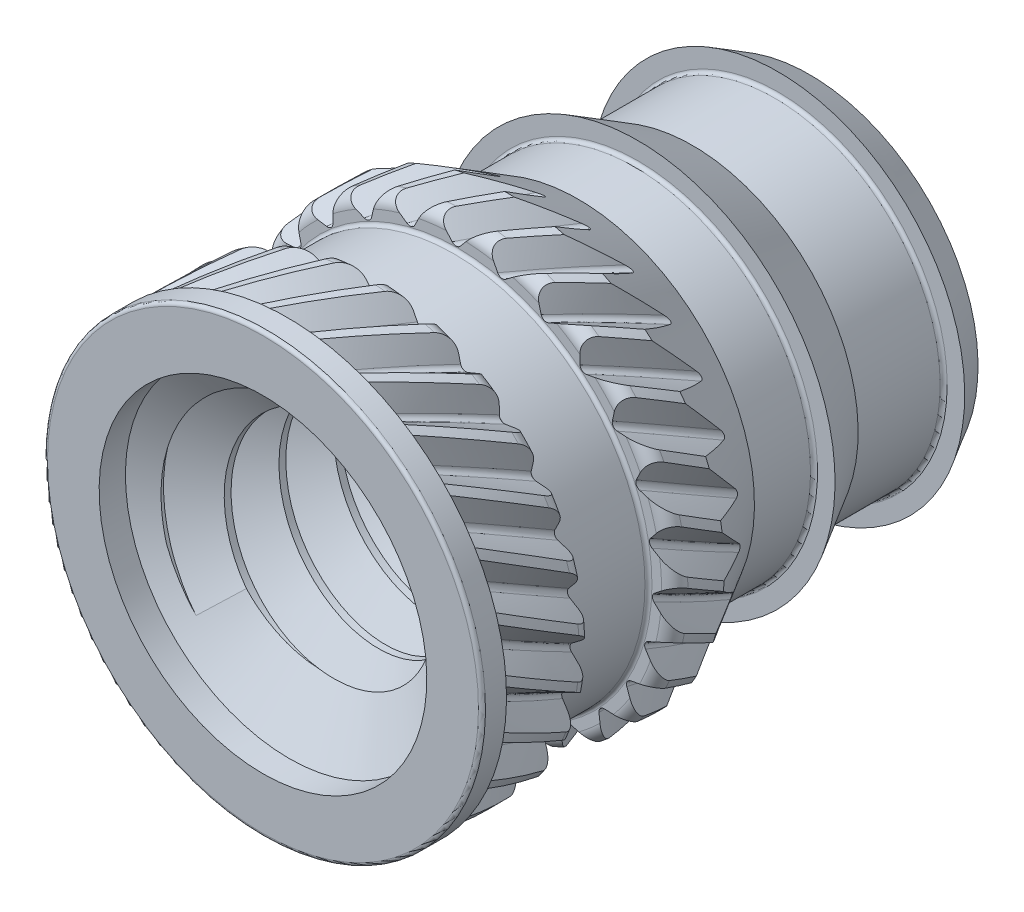
SolidWorks part; units mm, degrees
ref_plane "Front Plane" through (0, 0, 0) normal (0, 0, 1) x (1, 0, 0)
ref_plane "Top Plane" through (0, 0, 0) normal (0, 1, 0) x (1, 0, 0)
ref_plane "Right Plane" through (0, 0, 0) normal (1, 0, 0) x (0, 0, -1)
sketch "Sketch1" plane through (0, 0, 0) normal (1, 0, 0) x (0, 0, -1)
  line L0 (3.9624, 0) -> (-3.9624, 0) construction
  line L1 (-3.9624, 3.175) -> (-3.9624, -3.175) construction
  line L3 (3.9624, 2.4411) -> (3.9624, -2.4411) construction
  line L4 (-3.9624, 3.175) -> (-3.6068, 3.175) construction
  line L5 (-3.6068, 3.175) -> (-3.6068, 3.1496) construction
  line L6 (-3.6068, 3.1496) -> (-2.3368, 3.1496) construction
  line L7 (-2.3368, 3.1496) -> (-2.3368, 2.7686) construction
  line L8 (-2.3368, 2.7686) -> (-1.143, 2.7686) construction
  line L9 (-1.143, 2.7686) -> (-1.143, 3.1496) construction
  line L10 (-1.143, 3.1496) -> (-0.4243, 3.1496) construction
  line L12 (-3.5814, -2.3749) -> (-3.4128, -2.0828) construction
  line L13 (-3.4128, -2.0828) -> (3.8481, -2.0828) construction
  line L14 (3.8481, -2.0828) -> (3.9624, -2.1971) construction
  line L15 (-3.4128, -2.0828) -> (-3.4128, -1.2891) construction
  line L16 (-3.5814, -2.3749) -> (-3.9624, -2.3749) construction
  line L17 (-0.4243, 3.1496) -> (0.6096, 2.5527) construction
  line L18 (0.6096, 2.5527) -> (1.4732, 2.5527) construction
  line L19 (1.4732, 2.5527) -> (1.4732, 2.8575) construction
  line L20 (1.4732, 2.8575) -> (2.2651, 2.4003) construction
  line L21 (2.2651, 2.4003) -> (3.5052, 2.4003) construction
  line L22 (3.5052, 2.4003) -> (3.5052, 2.7051) construction
  line L23 (3.5052, 2.7051) -> (3.9624, 2.4411) construction
  point P4 (0, 0)
  dimension "Diameter (A)" = 6.35
  dimension "Installed Length" = 7.9248
  dimension "Head Length" = 0.3556
  dimension "Knurl Band OD" = 6.2992
  dimension "Knurl Band_1 Length" = 1.27
  dimension "Relief Depth" = 0.381
  dimension "Relief Length" = 1.1938
  dimension "Thread Size" = 4.1656
  dimension "Thread Pitch" = 0.7937
  dimension "C'Sink Dia (B)" = 4.3942
  dimension "C'Sink (A)" = 60
  dimension "C'Bore" = 4.7498
  dimension "C'Bore Depth" = 0.381
  dimension "Barb Angle" = 30
  dimension "End Barb Length" = 0.4572
  dimension "End Barb OD" = 5.4102
  dimension "End Barb Relief" = 4.8006
  dimension "Barb_2 OD" = 5.715
  dimension "Barbed Length" = 2.4892
  dimension "Barb_2 Relief" = 5.1054
  dimension "Barb_2 Relief Length" = 0.8636
  dimension "C'Sink (B)" = 45
sketch "Sketch2" plane through (0, 0, 0) normal (1, 0, 0) x (0, 0, -1)
  line L0 (-2.5273, 3.1496) -> (-2.5273, 2.7686) construction
  line L3 (3.5052, 2.7051) -> (3.9624, 2.4411) construction
  line L15 (3.5052, 2.4003) -> (3.5052, 2.7051) construction
  line L27 (2.2651, 2.4003) -> (3.5052, 2.4003) construction
  line L31 (1.4732, 2.8575) -> (2.2651, 2.4003) construction
  line L33 (1.4732, 2.5527) -> (1.4732, 2.8575) construction
  line L35 (0.6096, 2.5527) -> (1.4732, 2.5527) construction
  line L36 (-0.4243, 3.1496) -> (0.6096, 2.5527) construction
  line L37 (-1.143, 3.1496) -> (-0.4243, 3.1496) construction
  line L38 (-1.143, 2.7686) -> (-1.143, 3.1496) construction
  line L39 (-2.3368, 2.7686) -> (-1.143, 2.7686) construction
  line L40 (-2.3368, 3.1496) -> (-2.3368, 2.7686) construction
  line L41 (-3.6068, 3.1496) -> (-2.3368, 3.1496) construction
  line L42 (-3.6068, 3.175) -> (-3.6068, 3.1496) construction
  line L43 (-3.9624, 3.175) -> (-3.6068, 3.175) construction
  line L44 (3.5052, 2.7051) -> (3.9624, 2.4411)
  line L45 (3.5052, 2.4511) -> (3.5052, 2.7051)
  line L46 (2.2651, 2.4003) -> (3.4544, 2.4003)
  line L47 (1.4732, 2.8575) -> (2.2651, 2.4003)
  line L48 (1.4732, 2.6035) -> (1.4732, 2.8575)
  line L49 (0.6096, 2.5527) -> (1.4224, 2.5527)
  line L50 (-0.4243, 3.1496) -> (0.6096, 2.5527)
  line L51 (-0.9525, 3.1496) -> (-0.4243, 3.1496)
  line L52 (-1.143, 2.8194) -> (-1.143, 2.9591)
  line L53 (-2.286, 2.7686) -> (-1.1938, 2.7686)
  line L54 (-2.3368, 2.9591) -> (-2.3368, 2.8194)
  line L55 (-3.6068, 3.1496) -> (-2.5273, 3.1496)
  line L56 (-3.6068, 3.175) -> (-3.6068, 3.1496)
  line L57 (-3.9116, 3.175) -> (-3.6068, 3.175)
  line L58 (-3.9624, 0) -> (3.9624, 0) construction
  line L59 (-3.9624, 3.1242) -> (-3.9624, 2.3749)
  line L60 (-3.9624, 3.175) -> (-3.9624, -3.175) construction
  line L61 (-3.9624, 2.3749) -> (-3.5814, 2.3749)
  line L62 (-3.5814, 2.3749) -> (-3.4128, 2.0828)
  line L63 (-3.4128, 2.0828) -> (3.8481, 2.0828)
  line L64 (3.8481, 2.0828) -> (3.9624, 2.1971)
  line L65 (3.9624, 2.4411) -> (3.9624, -2.4411) construction
  line L66 (3.9624, 2.1971) -> (3.9624, 2.4411)
  line L67 (-3.5814, -2.3749) -> (-3.9624, -2.3749) construction
  line L68 (-3.5814, -2.3749) -> (-3.4128, -2.0828) construction
  line L69 (3.8481, -2.0828) -> (3.9624, -2.1971) construction
  line L70 (0, -2.0828) -> (0, 2.0828) construction
  line L71 (-3.4128, -2.0828) -> (3.8481, -2.0828) construction
  arc A1 (3.5052, 2.4511) -> (3.4544, 2.4003) centre (3.4544, 2.4511) cw
  arc A2 (1.4732, 2.6035) -> (1.4224, 2.5527) centre (1.4224, 2.6035) cw
  arc A3 (-0.9525, 3.1496) -> (-1.143, 2.9591) centre (-0.9525, 2.9591) ccw
  arc A4 (-2.3368, 2.9591) -> (-2.5273, 3.1496) centre (-2.5273, 2.9591) ccw
  arc A5 (-3.9116, 3.175) -> (-3.9624, 3.1242) centre (-3.9116, 3.1242) ccw
  arc A6 (-1.143, 2.8194) -> (-1.1938, 2.7686) centre (-1.1938, 2.8194) cw
  arc A7 (-2.286, 2.7686) -> (-2.3368, 2.8194) centre (-2.286, 2.8194) cw
  point P64 (0, 0)
  dimension "D1" = 0.0508
  dimension "D2" = 0.0508
  dimension "D3" = 0.0508
  dimension "Knurl Length" = 4.2164
revolve "Revolve1" add sketch "Sketch2" angle 360 about L58
sketch "Sketch3" plane through (0, 0, 0) normal (0, 0, 1) x (1, 0, 0)
  line L0 (0, -2.0828) -> (0, 0) construction
  line L1 (0, 0) -> (1.0414, -1.8038) construction
  line L2 (0, 2.4411) -> (0, -2.4411) construction
  circle A0 centre (0, 0) radius 2.0828 construction
  point P0 (1.0414, -1.8038)
  dimension "D1" = 30
sketch "Sketch4" plane through (0, 0, 3.9624) normal (0, 0, 1) x (1, 0, 0)
  circle A0 centre (0, 0) radius 2.0828 construction
  circle A1 centre (0, 0) radius 2.0828
curve "Helix/Spiral1" pitch 0.7937 height 8.7186 radius 2.0828 centre (0, 0, 3.9624) axis (0, 0, -1) start towards (0, 1, 0)
sketch "Sketch5" plane through (0, 0, 0) normal (1, 0, 0) x (0, 0, -1)
  line L0 (-4.7313, 2.1258) -> (-4.3345, 1.4384) construction
  line L1 (-4.3345, 1.4384) -> (-3.9376, 2.1258) construction
  line L2 (-3.9376, 2.1258) -> (-4.7313, 2.1258) construction
  line L3 (-4.6817, 2.0398) -> (-3.9872, 2.0398) construction
  line L4 (-4.3345, 2.1258) -> (-4.3345, 2.0398) construction
  line L5 (-4.3345, 2.0398) -> (-4.3345, 1.5243) construction
  line L6 (-4.3345, 1.5243) -> (-4.3345, 1.4384) construction
  line L7 (-4.3841, 1.5243) -> (-4.2849, 1.5243)
  line L8 (-4.7065, 2.0828) -> (-3.9624, 2.0828)
  line L9 (-4.2849, 1.5243) -> (-3.9624, 2.0828)
  line L10 (-4.3841, 1.5243) -> (-4.7065, 2.0828)
  line L15 (3.8481, 2.0828) -> (-3.4128, 2.0828) construction
  line L16 (-3.9624, 3.175) -> (-3.9624, -3.175) construction
  point P12 (-4.3345, 2.0828)
  dimension "D1" = 0.7937
  dimension "D2" = 0.0992
sweep "Sweep1" add profiles "Sketch5" path "Helix/Spiral1"
ref_plane "Plane1" through (0, 0, 3.5814) normal (0, 0, 1) x (1, 0, 0)
sketch "Sketch6" plane through (0, 0, 3.5814) normal (0, 0, 1) x (1, 0, 0)
  circle A0 centre (0, 0) radius 2.3749
extrude "Cut-Extrude1" cut sketch "Sketch6" against normal through all draft 60 and the other way through all
sketch "Sketch7" plane through (0, 0, -3.9624) normal (0, 0, -1) x (-1, 0, 0)
  circle A1 centre (0, 0) radius 2.1971
  circle A2 centre (0, 0) radius 2.1971 construction
extrude "Cut-Extrude2" cut sketch "Sketch7" against normal through all draft 45 and the other way through all
ref_plane "Plane2" through (0, 0, 3.6068) normal (0, 0, 1) x (1, 0, 0)
sketch "Sketch8" plane through (0, 0, 3.6068) normal (0, 0, 1) x (1, 0, 0)
  circle A1 centre (0, 0) radius 3.1496
  circle A2 centre (0, 0) radius 3.1496 construction
curve "Helix/Spiral2" pitch 33.7312 height 4.2164 radius 3.1496 centre (0, 0, 3.6068) axis (0, 0, -1) start towards (0, 1, 0)
sketch "Sketch9" plane through (0, 0, 3.6068) normal (0, 0, 1) x (1, 0, 0)
  line L0 (-0.317, 3.1591) -> (-0.0578, 2.8569)
  line L1 (0.0578, 2.8569) -> (0.317, 3.1591)
  line L3 (0, 0) -> (0, 2.9065) construction
  circle A0 centre (0, 0) radius 2.8575 construction
  circle A1 centre (0, 0) radius 2.8575 construction
  arc A2 (-0.317, 3.1591) -> (0.317, 3.1591) centre (0, 0) cw
  arc A3 (-0.0578, 2.8569) -> (0.0578, 2.8569) centre (0, 2.9065) ccw
  circle A5 centre (0, 0) radius 3.175 construction
  dimension "D1" = 0.0762
  dimension "D2" = 0.635
sweep "Cut-Sweep1" cut profiles "Sketch9" path "Helix/Spiral2" align with end faces yes
pattern_circular "CirPattern1" count 27 over 360 about axis through (0, 0, 3.9624) along (0, 0, 1) of "Cut-Sweep1"
equation "\"D3@Helix/Spiral1\"=\"Installed Length@Sketch1\" + \"Thread Pitch@Sketch1\""
equation "\"D4@Helix/Spiral1\"=\"Thread Pitch@Sketch1\""
equation "\"D2@Sketch5\" = \"D1@Sketch5\" / 8"
equation "\"D1@Sketch5\" = \"Thread Pitch@Sketch1\""
equation "\"D3@Helix/Spiral2\"=\"Knurl Length@Sketch2\""
equation "\"D3@Cut-Extrude1\"=\"C'Sink (A)@Sketch1\""
equation "\"D3@Cut-Extrude2\"=\"C'Sink (B)@Sketch1\""
equation "\"D2@Sketch9\"=\"Diameter (A)@Sketch1\" / 10"
equation "\"D1@CirPattern1\"= ( ( \"Diameter (A)@Sketch1\" * pi ) + 0.004 ) / ( ( 0.1 * \"Diameter (A)@Sketch1\" ) + 0.004 )"
